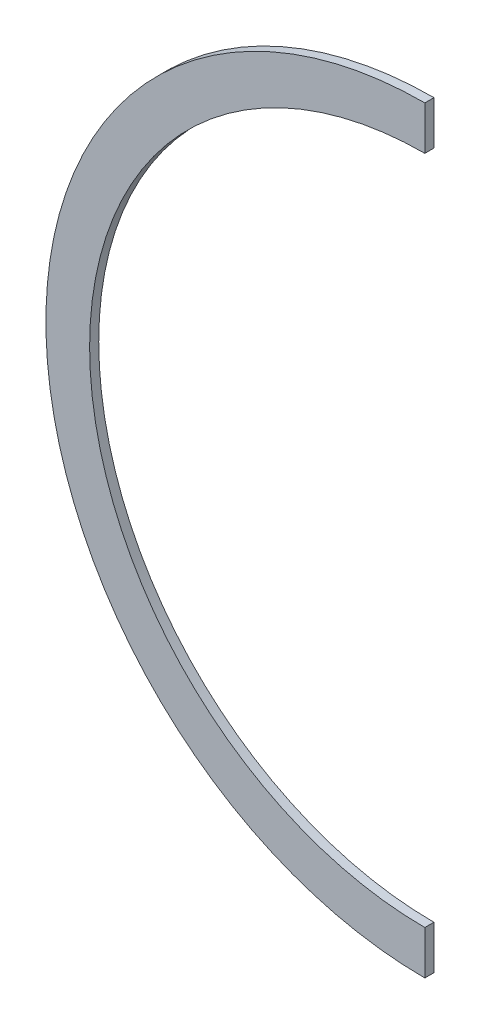
SolidWorks part; units mm, degrees
material "Balsa"
ref_plane "Front Plane" through (0, 0, 0) normal (0, 0, 1) x (1, 0, 0)
ref_plane "Top Plane" through (0, 0, 0) normal (0, 1, 0) x (1, 0, 0)
ref_plane "Right Plane" through (0, 0, 0) normal (1, 0, 0) x (0, 0, -1)
sketch "Sketch2" plane through (0, 0, 0) normal (0, 0, 1) x (1, 0, 0)
  line L0 (0, 0) -> (0, 236.6718) construction
  line L1 (-1.651, 128.5137) -> (-1.651, 121.4017) construction
  line L3 (1.651, 128.5137) -> (1.651, 121.4017) construction
  line L4 (-1.651, 121.4017) -> (1.651, 121.4017) construction
  line L5 (-136.2076, -77.8947) -> (0.0002, 0.7357) construction
  line L6 (-136.2076, -77.8947) -> (0.0002, 0.7357) construction
  line L7 (136.2041, -77.9016) -> (0.0002, 0.7357) construction
  line L8 (136.2041, -77.9016) -> (0.0002, 0.7357) construction
  line L9 (-116.9771, -64.8869) -> (-110.0184, -60.8698) construction
  line L10 (-115.4068, -67.7931) -> (-108.3675, -63.7295) construction
  line L11 (-110.0184, -60.8698) -> (-108.3675, -63.7295) construction
  line L12 (-117.5533, -65.2196) -> (-116.9771, -64.8869) construction
  line L13 (-115.9024, -68.0792) -> (-115.4068, -67.7931) construction
  line L14 (115.4068, -67.7931) -> (109.2475, -64.2371) construction
  line L15 (110.8985, -61.3775) -> (109.2475, -64.2371) construction
  line L16 (116.9771, -64.8869) -> (110.8985, -61.3775) construction
  arc A0 (-1.651, 128.5137) -> (-116.9771, -64.8869) centre (0, -3.556) ccw
  arc A1 (0.0665, 128.1531) -> (63.0696, -118.8475) centre (0, -3.3993) ccw construction
  circle A2 centre (0, -3.556) radius 116.84
  arc A3 (63.0696, -118.8475) -> (0.0665, 128.1531) centre (0, -3.3993) ccw construction
  arc A4 (0, 128.524) -> (-1.651, 128.5137) centre (0, -3.556) ccw
  circle A5 centre (0, -3.556) radius 132.08 construction
  arc A6 (1.651, 128.5137) -> (0, 128.524) centre (0, -3.556) ccw
  arc A7 (-116.9771, -64.8869) -> (-116.2009, -66.3452) centre (0, -3.556) ccw
  arc A8 (-115.4068, -67.7931) -> (115.4068, -67.7931) centre (0, -3.556) ccw
  arc A9 (-116.2009, -66.3452) -> (-115.4068, -67.7931) centre (0, -3.556) ccw
  arc A10 (115.4068, -67.7931) -> (116.1978, -66.3509) centre (0, -3.556) ccw
  arc A11 (116.9771, -64.8869) -> (1.651, 128.5137) centre (0, -3.556) ccw
  arc A12 (116.1978, -66.3509) -> (116.9771, -64.8869) centre (0, -3.556) ccw
  point P24 (-115.4068, -67.7931)
  dimension "D1" = 3.556
  dimension "D3" = 264.16
  dimension "D2" = 15.24
  dimension "D4" = 3.302
  dimension "D5" = 7.112
  dimension "D6" = 3.302
  dimension "D7" = 8.128
  dimension "D8" = 7.076
extrude "Boss-Extrude1" add sketch "Sketch2" along normal mid plane 3.175
sketch "Sketch3" plane through (0, 0, 0) normal (1, 0, 0) x (0, 0, -1)
  line L1 (-109.3908, 192.564) -> (122.8198, 192.564)
  line L2 (-109.3908, 192.564) -> (-109.3908, -206.3906)
  line L3 (-109.3908, -206.3906) -> (122.8198, -206.3906)
  line L4 (122.8198, 192.564) -> (122.8198, -206.3906)
extrude "Cut-Extrude1" cut sketch "Sketch3" along normal through all
